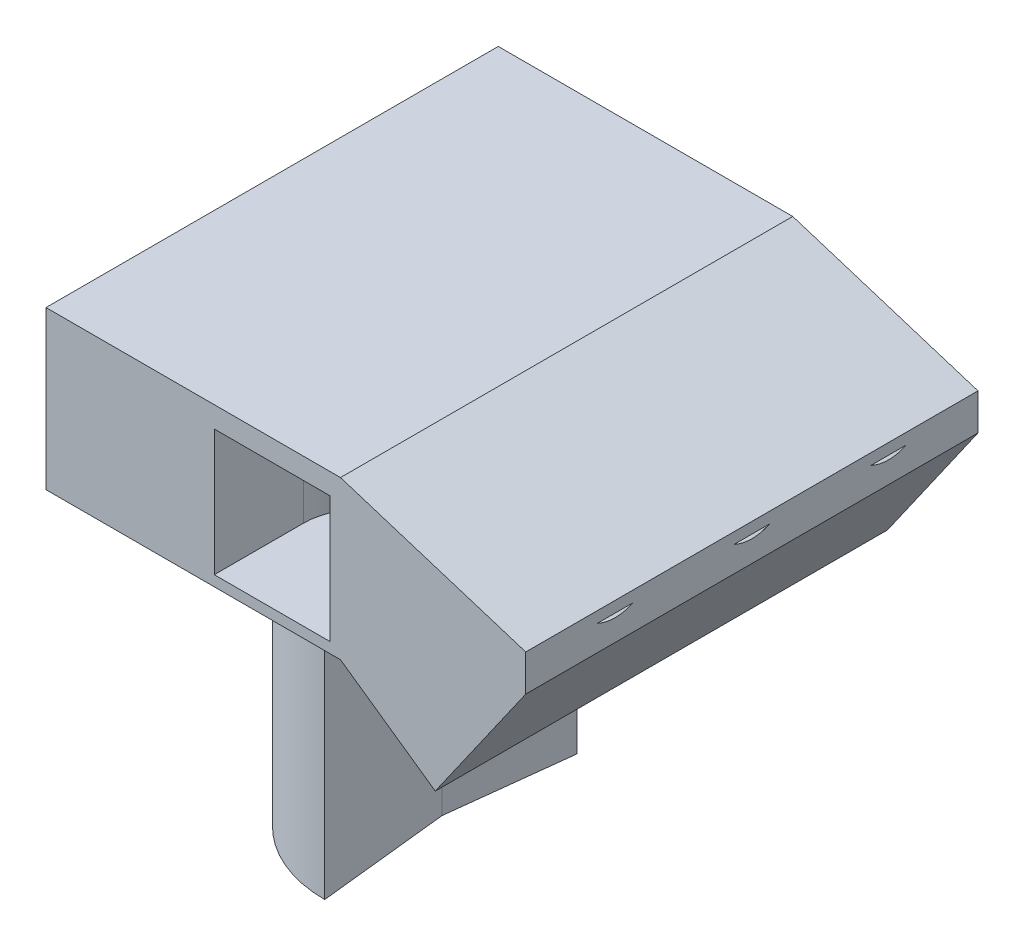
SolidWorks part; units mm, degrees
ref_plane "Front Plane" through (0, 0, 0) normal (0, 0, 1) x (1, 0, 0)
ref_plane "Top Plane" through (0, 0, 0) normal (0, 1, 0) x (1, 0, 0)
ref_plane "Right Plane" through (0, 0, 0) normal (1, 0, 0) x (0, 0, -1)
sketch "Sketch1" plane through (0, 0, 0) normal (0, 1, 0) x (1, 0, 0)
  line L0 (0, 0) -> (2.6, 0) construction
  line L5 (0, 0) -> (0, 2.6) construction
  line L6 (6.3, 0) -> (6.9, 0) construction
  line L11 (3.9, 6.9) -> (-1.7, 6.9)
  line L12 (6.9, 6.9) -> (6.9, -1.7)
  line L13 (3.9, -1.7) -> (-1.7, -1.7)
  line L14 (-1.7, 6.9) -> (-1.7, -1.7)
  line L15 (6.9, 6.9) -> (-1.7, -1.7) construction
  line L16 (6.9, -1.7) -> (-1.7, 6.9) construction
  line L17 (0, 6.3) -> (-1.7, 6.3)
  line L19 (-1.7, 4.1) -> (0, 4.1)
  line L20 (0, 4.1) -> (0, 3.7)
  line L21 (0, 3.7) -> (-1.7, 3.7)
  line L23 (-1.7, 1.5) -> (0, 1.5)
  line L24 (0, 1.5) -> (0, 1.1)
  line L25 (0, 1.1) -> (-1.7, 1.1)
  line L26 (0, -1.1) -> (-1.7, -1.1)
  line L27 (1.5, 0) -> (1.5, -1.7)
  line L28 (3.7, 0) -> (3.7, -1.7)
  line L29 (5.2, -1.1) -> (6.9, -1.1)
  line L31 (6.9, 1.1) -> (5.2, 1.1)
  line L32 (5.2, 1.1) -> (5.2, 1.5)
  line L33 (5.2, 1.5) -> (6.9, 1.5)
  line L35 (6.9, 3.7) -> (5.2, 3.7)
  line L36 (5.2, 3.7) -> (5.2, 4.1)
  line L37 (5.2, 4.1) -> (6.9, 4.1)
  line L39 (6.9, 6.3) -> (5.2, 6.3)
  line L40 (3.7, 6.9) -> (3.7, 5.2)
  line L41 (1.5, 6.9) -> (1.5, 5.2)
  line L42 (3.7, 5.2) -> (4.1, 5.2) construction
  line L47 (3.9, 5.2) -> (3.9, 6.9)
  line L48 (3.9, 5.2) -> (3.9, -1.7)
  line L49 (2.6, 5.2) -> (0, 2.6) construction
  line L50 (0, 2.6) -> (2.6, 0) construction
  line L51 (2.6, 0) -> (5.2, 2.6) construction
  line L52 (2.6, 5.2) -> (5.2, 2.6) construction
  line L53 (3.9, 6.9) -> (6.9, 6.9)
  line L58 (6.9, -1.7) -> (3.9, -1.7)
  circle A9 centre (0, 0) radius 1.1
  circle A18 centre (2.6, 0) radius 1.1
  circle A19 centre (5.2, 0) radius 1.1
  circle A20 centre (2.6, 2.6) radius 1.1
  circle A21 centre (5.2, 2.6) radius 1.1
  circle A22 centre (2.6, 5.2) radius 1.1
  circle A23 centre (5.2, 5.2) radius 1.1
  circle A24 centre (0, 2.6) radius 1.1
  circle A25 centre (0, 5.2) radius 1.1
  dimension "D1" = 3
  dimension "D2" = 2.6
  dimension "D6" = 2.2
  dimension "D4" = 0.6
  dimension "D5" = 3
  dimension "D3" = 2.6
  dimension "D8" = 0.6
extrude "Housing" add sketch "Sketch1" along normal blind 3 contours L14 L13 L48 L47 L11
sketch "Kink Projection" plane through (0, 0, 0) normal (0, 1, 0) x (1, 0, 0)
  line L23 (3.9, 5.2) -> (3.9, 6.9) construction
  line L24 (3.9, 5.2) -> (3.9, -1.7) construction
  line L25 (6.9, -1.7) -> (3.9, -1.7) construction
  line L26 (6.9, 6.9) -> (6.9, -1.7) construction
  line L27 (3.9, 6.9) -> (6.9, 6.9) construction
  line L51 (3.9, 5.2) -> (3.9, 6.9)
  line L52 (3.9, 5.2) -> (3.9, -1.7)
  line L53 (6.9, -1.7) -> (3.9, -1.7)
  line L54 (6.9, 6.9) -> (6.9, -1.7)
  line L55 (3.9, 6.9) -> (6.9, 6.9)
sketch "Tilted Magnet" plane through (0, 0, -6.9) normal (0, 0, -1) x (-1, 0, 0)
  line L0 (-3.9, 0) -> (1.7, 0)
  line L1 (-3.9, 0) -> (-7.4229, -2.4667)
  line L3 (-7.4229, 1.8892) -> (-3.9, 3)
  line L4 (-3.9, 0) -> (-3.9, 3)
  line L5 (-5.6207, 2.4575) -> (-3.9, 0)
  line L8 (-7.4229, 1.8892) -> (-7.4229, 1.1956)
  line L9 (1.7, 3) -> (-7.8293, 3) construction
  line L10 (-5.6207, 2.4575) -> (-7.4229, 1.1956)
  line L11 (-7.4229, 1.1956) -> (-5.7021, -1.2619)
  line L13 (-7.4229, -2.4667) -> (-7.4229, 1.1956)
  line M7 (-3.9, 3) -> (-3.9, 0)
  dimension "D1" = 162.5
  dimension "D2" = 2.2
extrude "Kink Housing" add sketch "Tilted Magnet" against normal up to surface (8.6 mm away) separate body contours L10 L11 L1 L5 | L3 L5 M7 | L10 L3 L8 region at (4.4736, 1.8192, -6.9) region at (5.6614, 0.5978, -6.9) region at (6.8222, 1.8474, -6.9) up to face at (1.1, 1.5, 1.7)
sketch "Sketch18" plane through (1.2831, 1.8324, 0) normal (-0.5736, -0.8192, 0) x (0.8192, -0.5736, 0)
  line L4 (5.3947, 1.7) -> (3.1947, 1.7)
  line L5 (3.1947, 1.7) -> (3.1947, -6.9)
  line L6 (3.1947, -6.9) -> (5.3947, -6.9)
  line L13 (5.6521, -3.7) -> (4.2596, -3.7) construction
  line L14 (4.2596, -3.7) -> (4.2596, -4.1) construction
  line L15 (4.2596, -4.1) -> (5.6521, -4.1) construction
  line L16 (5.6521, -1.1) -> (4.2596, -1.1) construction
  line L17 (4.2596, -1.1) -> (4.2596, -1.5) construction
  line L18 (4.2596, -1.5) -> (5.6521, -1.5) construction
  line L19 (4.2596, 1.1) -> (5.6521, 1.1) construction
  line L27 (5.6521, -6.3) -> (4.2596, -6.3) construction
  line L34 (5.6521, -6.9) -> (5.6521, 1.7) construction
  line L35 (3.1947, -6.9) -> (5.6521, -6.9) construction
  line L41 (5.6521, -3.7) -> (4.2596, -3.7)
  line L42 (4.2596, -3.7) -> (4.2596, -4.1)
  line L43 (4.2596, -4.1) -> (5.6521, -4.1)
  line L44 (5.6521, -1.1) -> (4.2596, -1.1)
  line L45 (4.2596, -1.1) -> (4.2596, -1.5)
  line L46 (4.2596, -1.5) -> (5.6521, -1.5)
  line L47 (4.2596, 1.1) -> (5.6521, 1.1)
  line L49 (3.1947, -6.9) -> (5.3947, -6.9)
  line L50 (5.3947, -6.9) -> (5.3947, 1.7)
  line L53 (5.3947, -6.9) -> (5.3947, 1.7)
  line L55 (5.6521, -6.3) -> (4.2596, -6.3)
  line L62 (5.6521, -6.9) -> (5.6521, 1.7)
  line L63 (3.1947, -6.9) -> (5.6521, -6.9)
  ellipse E3 centre (4.2596, -2.6) end of major axis (4.2596, -3.7) minor radius 0.9011
  ellipse E4 centre (4.2596, -2.6) end of major axis (4.2596, -3.7) minor radius 0.9011
  ellipse E7 centre (4.2596, 0) end of major axis (4.2596, 1.1) minor radius 0.9011
  ellipse E8 centre (4.2596, 0) end of major axis (4.2596, 1.1) minor radius 0.9011
  ellipse E17 centre (4.2596, -5.2) end of major axis (4.2596, -4.1) minor radius 0.9011
  ellipse E18 centre (4.2596, -5.2) end of major axis (4.2596, -4.1) minor radius 0.9011
  dimension "D1" = 0
  dimension "D3" = 0
  dimension "D5" = 0
  dimension "D10" = 0
extrude "Kink Slots" cut sketch "Sketch18" against normal offset from surface (3.1261 mm away) 0.2 contours E18 | E4 | E8 region at (4.7723, -0.6108, 0) region at (4.7723, -0.6108, -2.6) region at (4.7723, -0.6108, -5.2) up to face at (5.6614, 2.4446, -2.6)
extrude "Side Cuts" cut sketch "Sketch1<14>" along normal offset from surface (2.6 mm away) 0.2 from offset 0.2 contours A22 L40 L11 L41 | A22 | A25 | A25 L17 L14 L19 | A24 | A24 L21 L14 L23 | A18 | A18 L27 L13 L28 | A9 | A9 L25 L14 L26 region at (2.6, 0, -6.4459) region at (2.6, 0, -5.2) region at (2.6, 0, 1.2459) region at (-1.2459, 0, -5.2) region at (2.6, 0, 0) region at (0, 0, -5.2) region at (-1.2459, 0, -2.6) region at (-1.2459, 0, 0) region at (0, 0, -2.6) region at (0, 0, 0) up to face at (1.1, 3, -2.6)
sketch "Sketch1<14>" plane through (0, 0, 0) normal (0, 1, 0) x (1, 0, 0) same geometry as "Sketch1"
extrude "Center Cut" cut sketch "Sketch1<15>" along normal offset from surface (2.8 mm away) 0.2 contours A20 region at (2.6, 0, -2.6) up to face at (1.1, 3, -2.6)
sketch "Sketch1<15>" plane through (0, 0, 0) normal (0, 1, 0) x (1, 0, 0) same geometry as "Sketch1"
sketch "Sketch19" plane through (0, 3, 0) normal (0, 1, 0) x (1, 0, 0)
  line L0 (-1.7, -1.4408) -> (-1.4408, -1.4408) construction
  line L1 (-1.7, 6.9) -> (3.9, 6.9)
  line L2 (-1.7, 6.9) -> (-1.7, -1.7)
  line L3 (-1.7, -1.7) -> (3.9, -1.7)
  line L4 (3.9, 6.9) -> (3.9, -1.7)
  line L5 (3.9, 6.6408) -> (-1.4408, 6.6408)
  line L6 (3.9, 6.6408) -> (3.9, -1.4408)
  line L7 (3.9, -1.4408) -> (-1.4408, -1.4408)
  line L8 (-1.4408, 6.6408) -> (-1.4408, -1.4408)
  line L9 (3.9, 6.6408) -> (-1.4408, -1.4408) construction
  line L10 (3.9, -1.4408) -> (-1.4408, 6.6408) construction
  line L11 (-1.4408, -1.4408) -> (-1.4408, -1.7) construction
  line L12 (3.9, 5.2) -> (3.9, -1.7) construction
  line L13 (3.9, 6.6408) -> (3.9, 6.9) construction
  line L14 (3.9, 6.6408) -> (3.9, -1.4408)
  point P6 (1.2296, 2.6)
  line M6 (3.9, 6.9) -> (-1.7, 6.9)
  line M7 (-1.7, 6.9) -> (-1.7, -1.7)
  line M8 (-1.7, -1.7) -> (3.9, -1.7)
  line M9 (3.9, -1.7) -> (3.9, 6.9)
extrude "Boss-Extrude4" add sketch "Sketch19" against normal blind 0.2 from surface contours L8 L5 L4 L7 M6 M7 M8 M9 region at (1.1, 3, -6.7974) starting at face at (-0.575, 2.8, -5.2)
sketch "Sketch20" plane through (0, 0, 0) normal (0, -1, 0) x (1, 0, 0)
  line L0 (-1.7, -2.6) -> (-0.7, -2.6) construction
  line L1 (-1.7, -6.9) -> (-1.7, 1.7) construction
  line L2 (1.7, -0.2) -> (1.4329, -2.7)
  line L3 (1.4329, -2.7) -> (1.7, -5)
  circle A0 centre (1.7, -2.6) radius 2.4
  dimension "D2" = 4.8
  dimension "D1" = 1
extrude "Boss-Extrude5" add sketch "Sketch20" along normal blind 6 contours L2 A0 L3 region at (0.6105, 0, -2.5975)
